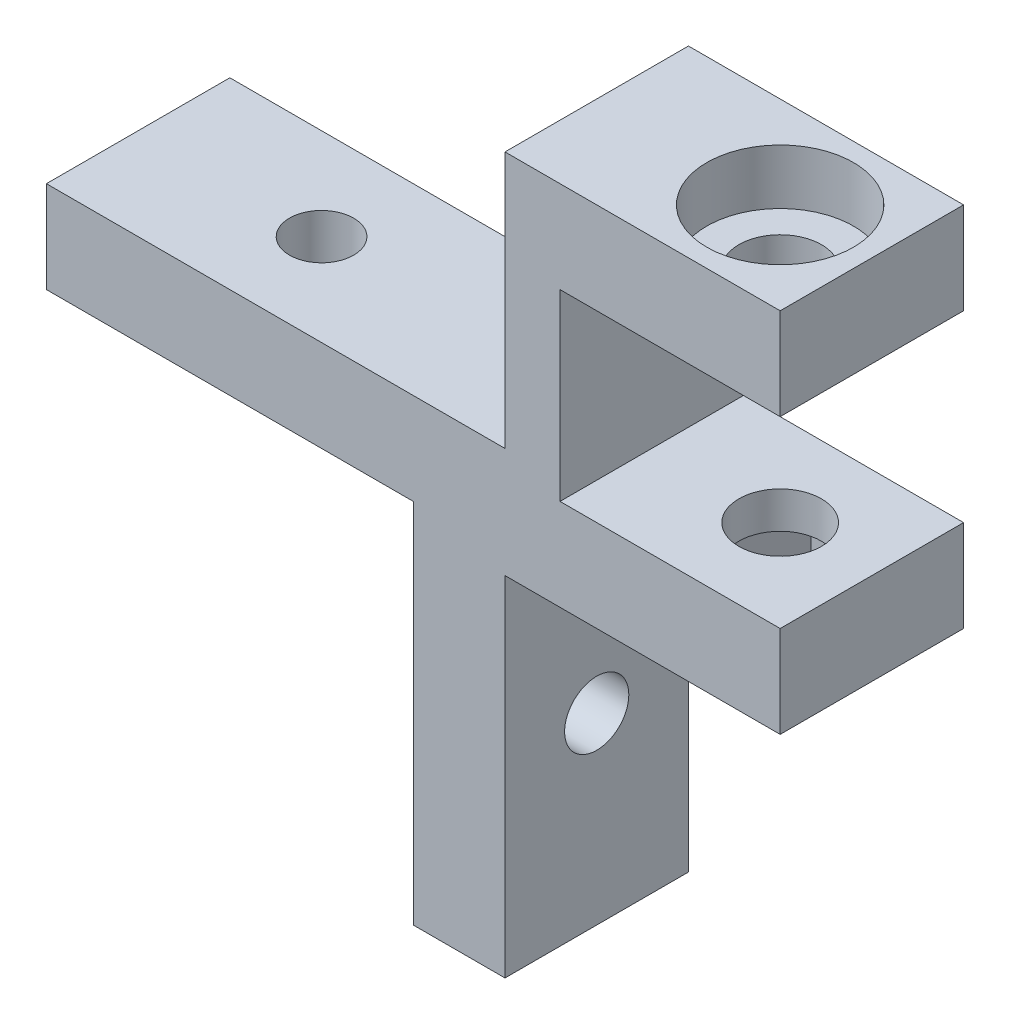
SolidWorks part; units mm, degrees
material "ABS"
ref_plane "Front Plane" through (0, 0, 0) normal (0, 0, 1) x (1, 0, 0)
ref_plane "Top Plane" through (0, 0, 0) normal (0, 1, 0) x (1, 0, 0)
ref_plane "Right Plane" through (0, 0, 0) normal (1, 0, 0) x (0, 0, -1)
sketch "Sketch2" plane through (0, 0, 0) normal (0, 0, 1) x (1, 0, 0)
  line L1 (-12.5, -12.5) -> (12.5, -12.5)
  line L2 (-12.5, -12.5) -> (-12.5, 12.5)
  line L3 (-12.5, 12.5) -> (12.5, 12.5)
  line L4 (12.5, -12.5) -> (12.5, 12.5)
  line L5 (-12.5, -12.5) -> (12.5, 12.5) construction
  line L6 (-12.5, 12.5) -> (12.5, -12.5) construction
  point P0 (0, 0)
  dimension "D1" = 25
  dimension "D2" = 25
extrude "Boss-Extrude1" add sketch "Sketch2" along normal blind 10
sketch "Sketch3" plane through (0, 0, 10) normal (0, 0, 1) x (1, 0, 0)
  line L1 (-12.5, -12.5) -> (7.5, -12.5)
  line L2 (-12.5, -12.5) -> (-12.5, 7.5)
  line L3 (-12.5, 7.5) -> (7.5, 7.5)
  line L4 (7.5, -12.5) -> (7.5, 7.5)
  dimension "D1" = 20
  dimension "D2" = 20
extrude "Cut-Extrude1" cut sketch "Sketch3" against normal through all
sketch "Sketch5" plane through (12.5, 0, 0) normal (1, 0, 0) x (0, 0, -1)
  line L0 (-10, -12.5) -> (-10, 12.5) construction
  line L1 (-10, 6.5) -> (0, 6.5)
  line L2 (-10, 6.5) -> (-10, 26.5)
  line L3 (-10, 26.5) -> (0, 26.5)
  line L4 (0, 6.5) -> (0, 26.5)
  line L5 (-10, 12.5) -> (0, 12.5) construction
  dimension "D1" = 14
  dimension "D2" = 6
extrude "Boss-Extrude2" add sketch "Sketch5" along normal blind 15
sketch "Sketch7" plane through (0, 0, 10) normal (0, 0, 1) x (1, 0, 0)
  line L0 (27.5, 26.5) -> (27.5, 6.5) construction
  line L1 (27.5, 21.5) -> (15.5, 21.5)
  line L2 (27.5, 21.5) -> (27.5, 11.5)
  line L3 (27.5, 11.5) -> (15.5, 11.5)
  line L4 (15.5, 21.5) -> (15.5, 11.5)
  line L5 (12.5, 12.5) -> (-12.5, 12.5) construction
  dimension "D1" = 10
  dimension "D2" = 1
  dimension "D3" = 12
extrude "Cut-Extrude2" cut sketch "Sketch7" against normal through all
sketch "Sketch8" plane through (0, 26.5, 0) normal (0, 1, 0) x (1, 0, 0)
  line L0 (12.5, -10) -> (12.5, 0) construction
  line L1 (27.5, 0) -> (12.5, 0) construction
  circle A0 centre (22.5, -5) radius 2.25
  dimension "D1" = 4.5
  dimension "D2" = 10
  dimension "D3" = 5
extrude "Cut-Extrude3" cut sketch "Sketch8" against normal through all
sketch "Sketch9" plane through (0, 12.5, 0) normal (0, 1, 0) x (1, 0, 0)
  line L0 (-12.5, -10) -> (-12.5, 0) construction
  line L2 (12.5, -10) -> (-12.5, -10) construction
  circle A0 centre (-2.5, -5) radius 1.75
  dimension "D1" = 3.5
  dimension "D2" = 10
  dimension "D3" = 5
extrude "Cut-Extrude4" cut sketch "Sketch9" against normal blind 15
sketch "Sketch10" plane through (12.5, 0, 0) normal (1, 0, 0) x (0, 0, -1)
  line L0 (-10, -12.5) -> (-10, 6.5) construction
  line L1 (-10, -12.5) -> (0, -12.5) construction
  circle A0 centre (-5, -2.5) radius 1.75
  dimension "D3" = 3.5
  dimension "D1" = 5
  dimension "D2" = 10
extrude "Cut-Extrude5" cut sketch "Sketch10" against normal blind 15
hole_wizard "CBORE for M4 Hex Socket Head Cap Screw1" positions "Sketch11" profile "Sketch12" counterbore size "M4" standard "ISO" end condition through all
sketch "Sketch11" plane through (0, 26.5, 0) normal (0, 1, 0) x (1, 0, 0)
  point P0 (22.5, -5)
sketch "Sketch12" plane through (22.5, 26.5, 5) normal (1, 0, 0) x (0, 0, 1)
  line L0 (0, 0) -> (0, 39)
  line L1 (0, 39) -> (2.25, 39)
  line L3 (2.25, 39) -> (2.25, 3)
  line L4 (2.25, 3) -> (4, 3)
  line L5 (4, 3) -> (4, 0)
  line L7 (4, 0) -> (0, 0)
  line L11 (0, -6.35) -> (0, 107.95) construction
  dimension "Thru Hole Dia." = 4.5
  dimension "Thru Hole Depth" = 39
  dimension "C'Bore Dia." = 8
  dimension "C'Bore Depth" = 3
sketch "Sketch13" plane through (0, 6.5, 0) normal (0, -1, 0) x (1, 0, 0)
  line L1 (17.8812, 5) -> (20.1906, 1)
  line L2 (20.1906, 1) -> (24.8094, 1)
  line L3 (24.8094, 1) -> (27.1188, 5)
  line L4 (27.1188, 5) -> (24.8094, 9)
  line L5 (24.8094, 9) -> (20.1906, 9)
  line L6 (20.1906, 9) -> (17.8812, 5)
  circle A0 centre (22.5, 5) radius 4 construction
  dimension "D1" = 8
extrude "Cut-Extrude6" cut sketch "Sketch13" against normal blind 3
